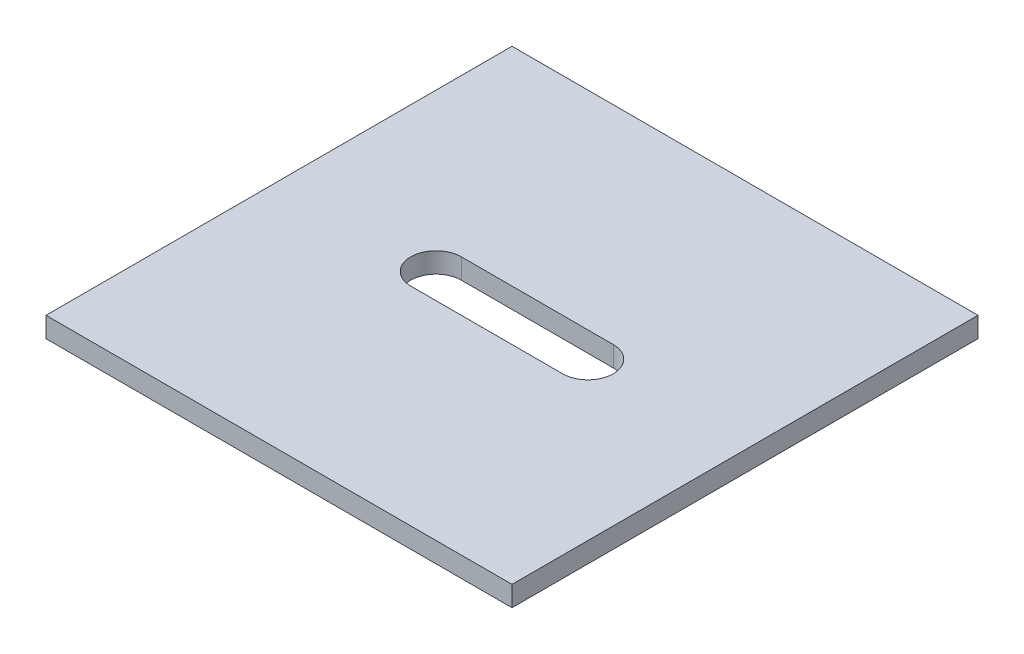
SolidWorks part; units mm, degrees
material "Pine"
ref_plane "Front Plane" through (0, 0, 0) normal (0, 0, 1) x (1, 0, 0)
ref_plane "Top Plane" through (0, 0, 0) normal (0, 1, 0) x (1, 0, 0)
ref_plane "Right Plane" through (0, 0, 0) normal (1, 0, 0) x (0, 0, -1)
sketch "Sketch2" plane through (0, 0, 0) normal (0, 1, 0) x (1, 0, 0)
  line L4 (93, 138) -> (183, 138) construction
  line L5 (0, 0) -> (276, 0)
  line L6 (0, 0) -> (0, 276)
  line L7 (0, 276) -> (276, 276)
  line L8 (276, 0) -> (276, 276)
  line L9 (93, 153) -> (183, 153)
  line L10 (93, 123) -> (183, 123)
  arc A0 (93, 153) -> (93, 123) centre (93, 138) ccw
  arc A1 (183, 123) -> (183, 153) centre (183, 138) ccw
  point P7 (138, 138)
  dimension "D3" = 138
  dimension "D5" = 15
  dimension "D1" = 276
  dimension "D2" = 276
  dimension "D4" = 93
  dimension "D6" = 90
extrude "Boss-Extrude1" add sketch "Sketch2" along normal blind 12 contours L7 L8 L5 L6
extrude "Cut-Extrude1" cut sketch "Sketch2<3>" along normal up to surface (12 mm away) contours A0 L10 A1 L9 up to face at (138, 12, -138)
sketch "Sketch2<3>" plane through (0, 0, 0) normal (0, 1, 0) x (1, 0, 0) same geometry as "Sketch2"
equation "\"LENGTH\" = 900mm"
equation "\"PLY\"= 12mm"
equation "\"D1@Boss-Extrude1\"=\"PLY\""
